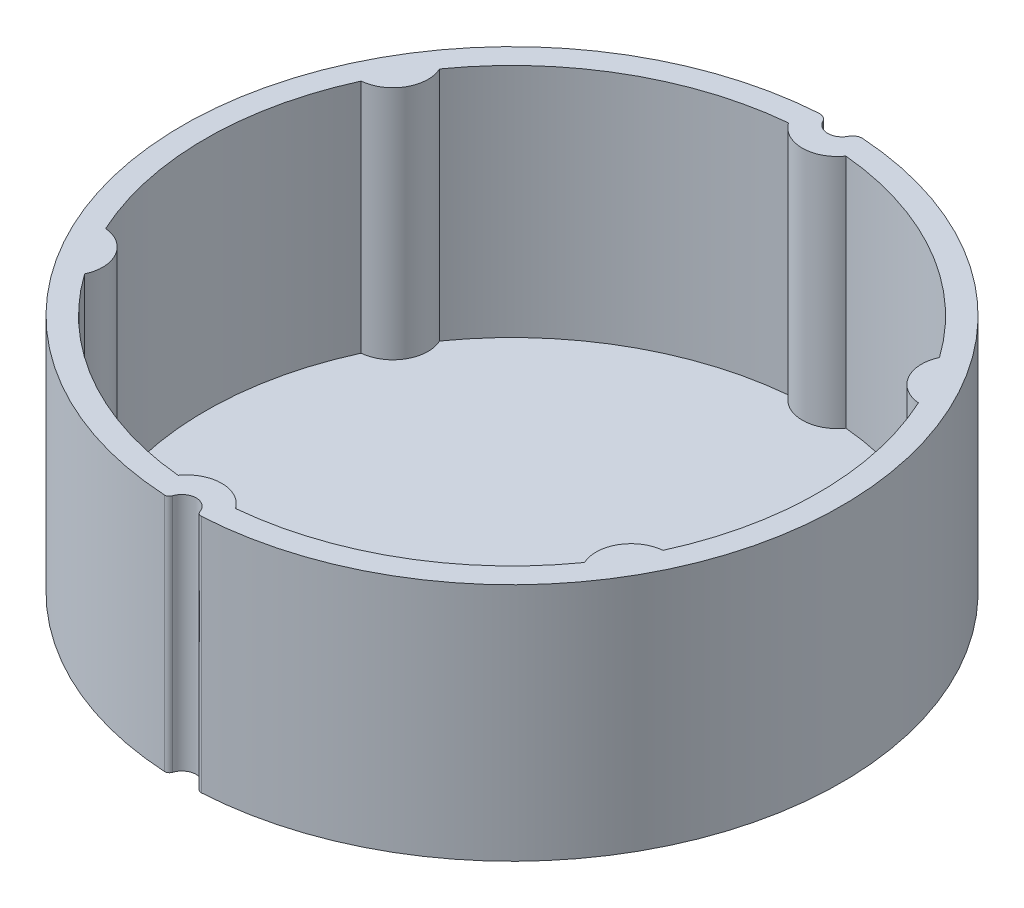
SolidWorks part; units mm, degrees
ref_plane "Front Plane" through (0, 0, 0) normal (0, 0, 1) x (1, 0, 0)
ref_plane "Top Plane" through (0, 0, 0) normal (0, 1, 0) x (1, 0, 0)
ref_plane "Right Plane" through (0, 0, 0) normal (1, 0, 0) x (0, 0, -1)
sketch "Sketch1" plane through (0, 0, 0) normal (0, 1, 0) x (1, 0, 0)
  line L3 (0, 0) -> (0, 3.1872) construction
  line L4 (0, 3.1872) -> (2.417, 3.1872)
  line L5 (0, 3.1872) -> (-2.417, 3.1872)
  line L6 (0, 32.9542) -> (0, 0) construction
  line L7 (0, 0) -> (-0.0105, -32.9541) construction
  arc A0 (1.9225, -34.3462) -> (2.2975, 34.3232) centre (0, 0) ccw
  arc A2 (-2.417, 3.1872) -> (2.417, 3.1872) centre (0, 0) ccw
  circle A3 centre (0, 0) radius 34.4 construction
  arc A7 (-1.3384, 33.7769) -> (1.3384, 33.7769) centre (0, 34.4542) ccw
  arc A9 (-2.2975, 34.3232) -> (-1.9445, -34.345) centre (0, 0) ccw
  arc A11 (1.3384, 33.7769) -> (2.2975, 34.3232) centre (2.2307, 33.3254) cw
  arc A12 (-1.3384, 33.7769) -> (-2.2975, 34.3232) centre (-2.2307, 33.3254) ccw
  arc A13 (1.4182, -33.9988) -> (-1.44, -33.9979) centre (-0.011, -34.4541) ccw
  arc A14 (1.4182, -33.9988) -> (1.9225, -34.3462) centre (1.8946, -33.847) ccw
  arc A15 (-1.44, -33.9979) -> (-1.9445, -34.345) centre (-1.9163, -33.8458) cw
  point P15 (1.4997, 33.97)
  dimension "D2" = 4.834
  dimension "D3" = 4
  dimension "D4" = 34.4
  dimension "D5" = 1
  dimension "D6" = 1.5
  dimension "D7" = 0.5
  dimension "D8" = 1.5
  dimension "D9" = 1.9335
  dimension "D11" = 1.4997
sketch "Sketch2"
  line L0 (0, 32.5) -> (0, 30.5) construction
  line L1 (28.1458, 16.25) -> (26.4138, 15.25) construction
  line L2 (28.1458, -16.25) -> (26.4138, -15.25) construction
  line L3 (0, -32.5) -> (0, -30.5) construction
  line L4 (-28.1458, -16.25) -> (-26.4138, -15.25) construction
  line L5 (-28.1458, 16.25) -> (-26.4138, 15.25) construction
  arc A16 (-1.9991, 32.4385) -> (-28.1458, 16.25) centre (0, 0) ccw
  arc A17 (1.9991, 32.4385) -> (-1.9991, 32.4385) centre (0, 32.5) cw
  arc A18 (29.0921, 14.488) -> (27.093, 17.9505) centre (28.1458, 16.25) cw
  arc A19 (27.093, -17.9505) -> (29.0921, -14.488) centre (28.1458, -16.25) cw
  arc A20 (-1.9991, -32.4385) -> (1.9991, -32.4385) centre (0, -32.5) cw
  arc A21 (-29.0921, -14.488) -> (-27.093, -17.9505) centre (-28.1458, -16.25) cw
  arc A22 (-27.093, 17.9505) -> (-29.0921, 14.488) centre (-28.1458, 16.25) cw
  arc A23 (27.093, 17.9505) -> (0, 32.5) centre (0, 0) ccw
  arc A24 (29.0921, -14.488) -> (28.1458, 16.25) centre (0, 0) ccw
  arc A25 (0, -32.5) -> (28.1458, -16.25) centre (0, 0) ccw
  arc A26 (-27.093, -17.9505) -> (-1.9991, -32.4385) centre (0, 0) ccw
  arc A27 (-29.0921, 14.488) -> (-28.1458, -16.25) centre (0, 0) ccw
  point P29 (0, 0)
  dimension "D1" = 65
  dimension "D2" = 2
  dimension "D3" = 6
sketch "Sketch2<2>" plane through (0, 0, 0) normal (0, 1, 0) x (1, 0, 0) same geometry as "Sketch2"
extrude "Boss-Extrude1" add sketch "Sketch1" along normal blind 25 contours A0 A7 A9 A2 L5 L4 region at (2.1624, 0, 33.4583)
sketch "Sketch5" plane through (0, 0, 0) normal (0, -1, 0) x (1, 0, 0)
  line L4 (-2.7327, -4.1872) -> (0, -4.1872)
  line L5 (0, -4.1872) -> (2.7327, -4.1872)
  line L6 (-2.7327, -4.1872) -> (0, -4.1872)
  line L7 (0, -4.1872) -> (2.7327, -4.1872)
  arc A2 (2.7327, -4.1872) -> (-2.7327, -4.1872) centre (0, 0) ccw
  arc A3 (2.7327, -4.1872) -> (-2.7327, -4.1872) centre (0, 0) ccw
  dimension "D1" = 1
extrude "Boss-Extrude2" add sketch "Sketch5" against normal up to surface (25 mm away) up to face at (-0.0041, 25, 0.0616)
sketch "Sketch6" plane through (0, 25, 0) normal (0, 1, 0) x (1, 0, 0)
  circle A0 centre (0, 0) radius 32
  dimension "D1" = 64
extrude "Cut-Extrude2" cut sketch "Sketch6" against normal offset from surface (24.6 mm away) 0.4 up to face at (-0.0041, 0, 0.0616)
sketch "Sketch8" plane through (0, 0.4, 0) normal (0, 1, 0) x (1, 0, 0)
  line L0 (0, 0) -> (0, 32) construction
  circle A0 centre (0, 0) radius 32 construction
  arc A1 (3, 31.8591) -> (-3, 31.8591) centre (0, 33.9659) cw
  arc A2 (-3, 31.8591) -> (3, 31.8591) centre (0, 0) cw
  point P8 (0, 30.3)
  point P10 (0, 32)
  dimension "D1" = 6
  dimension "D2" = 1.7
extrude "Boss-Extrude5" add sketch "Sketch8" along normal up to surface (24.6 mm away) up to face at (0, 25, 32)
pattern_circular "CirPattern1" count 6 over 360 about axis through (0, -90.5097, 0) along (0, 1, 0) of "Boss-Extrude5" reverse direction yes
